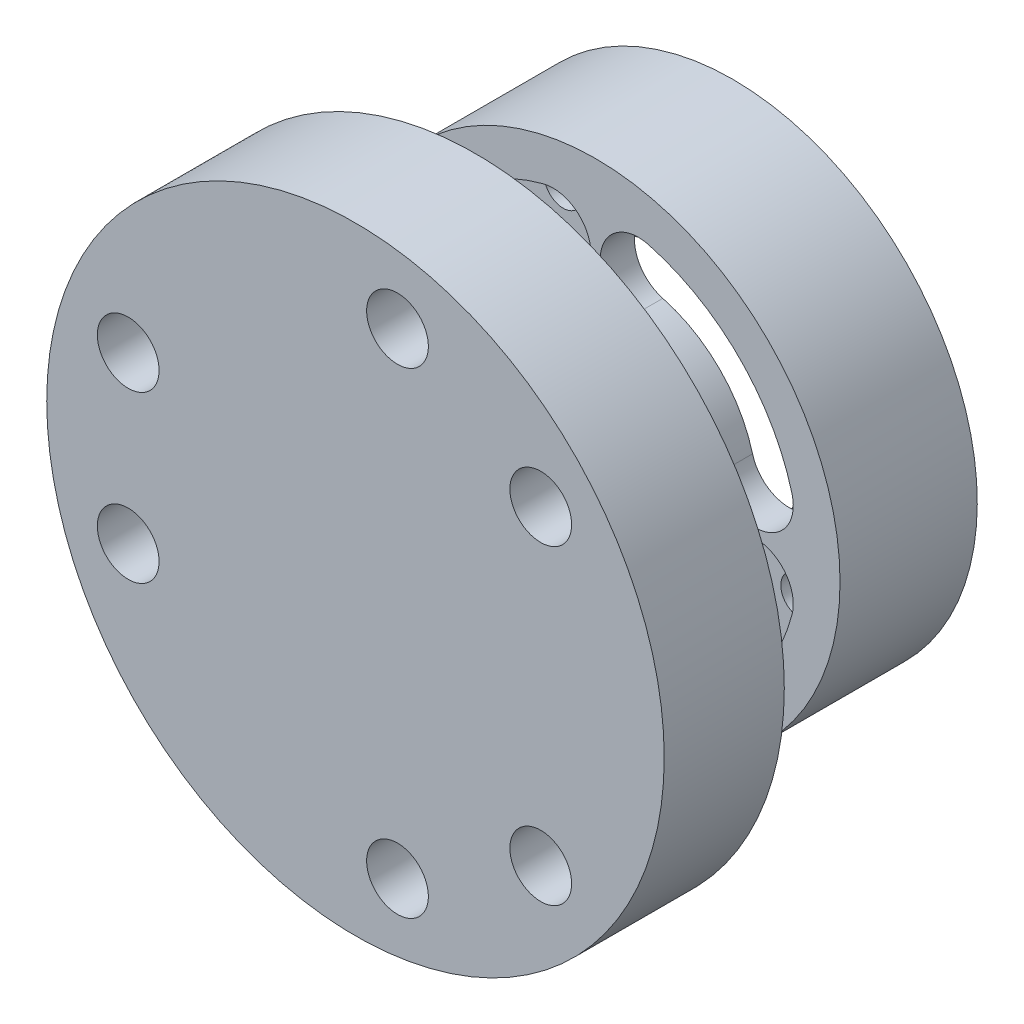
SolidWorks part; units mm, degrees
ref_plane "정면" through (0, 0, 0) normal (0, 0, 1) x (1, 0, 0)
ref_plane "윗면" through (0, 0, 0) normal (0, 1, 0) x (1, 0, 0)
ref_plane "우측면" through (0, 0, 0) normal (1, 0, 0) x (0, 0, -1)
sketch "스케치1" plane through (0, 0, 0) normal (0, 0, 1) x (1, 0, 0)
  line L0 (0, 0) -> (6.8943, 6.8943) construction
  line L1 (0, 0) -> (9.75, 0) construction
  line L2 (-4.25, -5.5621) -> (-4.25, -13.6015)
  line L3 (0, 0) -> (0, -14.25) construction
  line L4 (4.25, -5.5621) -> (4.25, -13.6015)
  arc A0 (4.25, -13.6015) -> (-4.25, -13.6015) centre (0, 0) ccw
  circle A1 centre (6.8943, 6.8943) radius 1.1
  circle A2 centre (0, 9.75) radius 2.1 construction
  circle A3 centre (0, 0) radius 9.75 construction
  arc A4 (4.25, -5.5621) -> (-4.25, -5.5621) centre (0, 0) ccw
  circle A5 centre (6.8943, -6.8943) radius 1.1
  circle A6 centre (-6.8943, -6.8943) radius 1.1
  circle A7 centre (-6.8943, 6.8943) radius 1.1
  point P19 (0, 0)
  dimension "D1" = 28.5
  dimension "D2" = 4.2
  dimension "D6" = 2.2
  dimension "D7" = 4.25
  dimension "D3" = 19.5
  dimension "D4" = 14
  dimension "D5" = 45
extrude "보스-돌출1" add sketch "스케치1" along normal blind 3
sketch "스케치2" plane through (0, 0, 3) normal (0, 0, 1) x (1, 0, 0)
  circle A0 centre (-6.8943, 6.8943) radius 2.1
  circle A1 centre (6.8943, 6.8943) radius 2.1
  circle A2 centre (6.8943, -6.8943) radius 2.1
  circle A3 centre (-6.8943, -6.8943) radius 2.1
  point P11 (0, 0)
  dimension "D2" = 4.2
  dimension "D1" = 4
extrude "컷-돌출1" [suppressed] cut sketch "스케치2" against normal blind 1.2
sketch "스케치3" plane through (0, 0, 3) normal (0, 0, 1) x (1, 0, 0)
  circle A0 centre (0, 0) radius 14.25
  circle A1 centre (0, 0) radius 11.85
  dimension "D1" = 28.5
  dimension "D2" = 23.7
extrude "보스-돌출2" add sketch "스케치3" along normal blind 1
sketch "스케치4" plane through (0, 0, 4) normal (0, 0, 1) x (1, 0, 0)
  line L0 (0, 0) -> (0, 14.25) construction
  line L1 (0, 0) -> (10.0763, 10.0763) construction
  line L2 (0, 0) -> (2.4911, 9.297) construction
  line L3 (2.7271, 4.9197) -> (0, 0) construction
  circle A0 centre (0, 0) radius 14.25
  arc A1 (2.4911, 9.297) -> (9.297, 2.4911) centre (0, 0) cw construction
  arc A2 (11.4462, 3.067) -> (3.067, 11.4462) centre (0, 0) ccw
  arc A3 (7.1479, 1.9153) -> (1.9153, 7.1479) centre (0, 0) ccw
  arc A4 (7.1479, 1.9153) -> (11.4462, 3.067) centre (9.297, 2.4911) ccw
  arc A5 (3.067, 11.4462) -> (1.9153, 7.1479) centre (2.4911, 9.297) ccw
  arc A6 (4.25, -11.0616) -> (-4.25, -11.0616) centre (0, 0) ccw construction
  arc A7 (-2.7271, 4.9197) -> (2.7271, 4.9197) centre (0, 0) cw construction
  circle A8 centre (0, 0) radius 11.85 construction
  circle A9 centre (0, 0) radius 3.25 construction
  circle A10 centre (0, 0) radius 4 construction
  arc A12 (9.297, -2.4911) -> (2.4911, -9.297) centre (0, 0) cw construction
  arc A13 (3.067, -11.4462) -> (11.4462, -3.067) centre (0, 0) ccw
  arc A14 (1.9153, -7.1479) -> (7.1479, -1.9153) centre (0, 0) ccw
  arc A15 (1.9153, -7.1479) -> (3.067, -11.4462) centre (2.4911, -9.297) ccw
  arc A16 (11.4462, -3.067) -> (7.1479, -1.9153) centre (9.297, -2.4911) ccw
  arc A17 (-2.4911, -9.297) -> (-9.297, -2.4911) centre (0, 0) cw construction
  arc A18 (-11.4462, -3.067) -> (-3.067, -11.4462) centre (0, 0) ccw
  arc A19 (-7.1479, -1.9153) -> (-1.9153, -7.1479) centre (0, 0) ccw
  arc A20 (-7.1479, -1.9153) -> (-11.4462, -3.067) centre (-9.297, -2.4911) ccw
  arc A21 (-3.067, -11.4462) -> (-1.9153, -7.1479) centre (-2.4911, -9.297) ccw
  arc A22 (-9.297, 2.4911) -> (-2.4911, 9.297) centre (0, 0) cw construction
  arc A23 (-3.067, 11.4462) -> (-11.4462, 3.067) centre (0, 0) ccw
  arc A24 (-1.9153, 7.1479) -> (-7.1479, 1.9153) centre (0, 0) ccw
  arc A25 (-1.9153, 7.1479) -> (-3.067, 11.4462) centre (-2.4911, 9.297) ccw
  arc A26 (-11.4462, 3.067) -> (-7.1479, 1.9153) centre (-9.297, 2.4911) ccw
  arc A27 (3.3937, 6.1223) -> (-3.3937, 6.1223) centre (0, 0) ccw
  arc A28 (2.0604, 3.7171) -> (-2.0604, 3.7171) centre (0, 0) ccw
  arc A29 (2.0604, 3.7171) -> (3.3937, 6.1223) centre (2.7271, 4.9197) ccw
  arc A30 (-3.3937, 6.1223) -> (-2.0604, 3.7171) centre (-2.7271, 4.9197) ccw
  arc A31 (4.9197, 2.7271) -> (4.9197, -2.7271) centre (0, 0) cw construction
  arc A32 (6.1223, -3.3937) -> (6.1223, 3.3937) centre (0, 0) ccw
  arc A33 (3.7171, -2.0604) -> (3.7171, 2.0604) centre (0, 0) ccw
  arc A34 (3.7171, -2.0604) -> (6.1223, -3.3937) centre (4.9197, -2.7271) ccw
  arc A35 (6.1223, 3.3937) -> (3.7171, 2.0604) centre (4.9197, 2.7271) ccw
  arc A36 (2.7271, -4.9197) -> (-2.7271, -4.9197) centre (0, 0) cw construction
  arc A37 (-3.3937, -6.1223) -> (3.3937, -6.1223) centre (0, 0) ccw
  arc A38 (-2.0604, -3.7171) -> (2.0604, -3.7171) centre (0, 0) ccw
  arc A39 (-2.0604, -3.7171) -> (-3.3937, -6.1223) centre (-2.7271, -4.9197) ccw
  arc A40 (3.3937, -6.1223) -> (2.0604, -3.7171) centre (2.7271, -4.9197) ccw
  arc A41 (-4.9197, -2.7271) -> (-4.9197, 2.7271) centre (0, 0) cw construction
  arc A42 (-6.1223, 3.3937) -> (-6.1223, -3.3937) centre (0, 0) ccw
  arc A43 (-3.7171, 2.0604) -> (-3.7171, -2.0604) centre (0, 0) ccw
  arc A44 (-3.7171, 2.0604) -> (-6.1223, 3.3937) centre (-4.9197, 2.7271) ccw
  arc A45 (-6.1223, -3.3937) -> (-3.7171, -2.0604) centre (-4.9197, -2.7271) ccw
  point P6 (6.8059, 6.8059)
  point P14 (7, 1.9953)
  point P18 (1.9171, 7.1545)
  point P28 (6.8059, -6.8059)
  point P35 (-6.8059, -6.8059)
  point P42 (-6.8059, 6.8059)
  point P47 (0, 0)
  point P48 (0, 5.625)
  point P53 (0, 0)
  point P54 (7.1064, 2.0604)
  point P59 (5.625, 0)
  point P66 (0, -5.625)
  point P73 (-5.625, 0)
  point P78 (0, 0)
  dimension "D2" = 28.5
  dimension "D3" = 6.5
  dimension "D4" = 8
  dimension "D5" = 30
  dimension "D7" = 7.4
  dimension "D8" = 7
  dimension "D9" = 4.25
  dimension "D1" = 45
  dimension "D10" = 29
  dimension "D6" = 4
extrude "보스-돌출3" add sketch "스케치4" along normal blind 4
sketch "스케치5" plane through (0, 0, 4) normal (0, 0, -1) x (-1, 0, 0)
  circle A0 centre (0, 0) radius 3.25
  dimension "D1" = 6.5
extrude "컷-돌출2" cut sketch "스케치5" against normal blind 2.5
sketch "스케치6" plane through (0, 0, 8) normal (0, 0, 1) x (1, 0, 0)
  circle A0 centre (0, 0) radius 3.5
  dimension "D1" = 7
extrude "보스-돌출4" add sketch "스케치6" along normal blind 7
sketch "스케치10" plane through (0, 0, 4) normal (0, 0, -1) x (-1, 0, 0)
  circle A0 centre (0, 0) radius 4.25
  circle A1 centre (0, 0) radius 11.85
extrude "컷-돌출3" cut sketch "스케치10" against normal blind 2
sketch "스케치7" plane through (0, 0, 15) normal (0, 0, 1) x (1, 0, 0)
  line L0 (0, 0) -> (-14.1, 0) construction
  line L1 (0, 0) -> (-13.2497, 4.8225) construction
  circle A0 centre (0, 0) radius 14.1 construction
  circle A1 centre (-13.2497, 4.8225) radius 1.6
  circle A2 centre (0, 0) radius 18
  circle A3 centre (-13.2497, -4.8225) radius 1.6
  circle A4 centre (10.8012, 9.0633) radius 1.6
  circle A5 centre (2.4484, 13.8858) radius 1.6
  circle A6 centre (2.4484, -13.8858) radius 1.6
  circle A7 centre (10.8012, -9.0633) radius 1.6
  point P20 (0, 0)
  dimension "D1" = 28.2
  dimension "D3" = 3.2
  dimension "D4" = 36
  dimension "D2" = 20
extrude "보스-돌출5" add sketch "스케치7" along normal blind 7
sketch "스케치8" plane through (0, 0, 15) normal (0, 0, -1) x (-1, 0, 0)
  circle A0 centre (13.2497, 4.8225) radius 2.75
  circle A1 centre (13.2497, -4.8225) radius 2.75
  circle A2 centre (-2.4484, -13.8858) radius 2.75
  circle A3 centre (-10.8012, -9.0633) radius 2.75
  circle A4 centre (-10.8012, 9.0633) radius 2.75
  circle A5 centre (-2.4484, 13.8858) radius 2.75
  point P17 (0, 0)
  dimension "D1" = 5.5
  dimension "D2" = 5.5
hole_wizard "M3 접시 머리 나사용 카운터싱크1" positions "3D스케치1" profile "스케치9" countersink size "M3" standard "ISO" end condition through all
sketch3d "3D스케치1"
  point P0 (2.4484, 13.8858, 15)
  point P3 (-13.2497, 4.8225, 15)
  point P6 (-13.2497, -4.8225, 15)
  point P9 (2.4484, -13.8858, 15)
  point P12 (10.8012, -9.0633, 15)
  point P15 (10.8012, 9.0633, 15)
sketch "스케치9" plane through (2.4484, 13.8858, 15) normal (1, 0, 0) x (0, 1, 0)
  line L0 (0, 0) -> (0, 7)
  line L1 (0, 7) -> (1.8, 7)
  line L2 (1.8, 7) -> (1.8, 1.35)
  line L3 (1.8, 1.35) -> (3.15, 0)
  line L5 (3.15, 0) -> (0, 0)
  line L6 (-1.8, 1.35) -> (-3.15, 0) construction
  line L11 (0, -6.35) -> (0, 107.95) construction
  dimension "관통 구멍 지름" = 3.6
  dimension "관통 구멍 깊이" = 7
  dimension "표면 카운터싱크 지름" = 6.3
  dimension "표면 카운터싱크 각도" = 90
ref_axis "기준축1" through (0, 0, 22) along (0, 0, -1)
